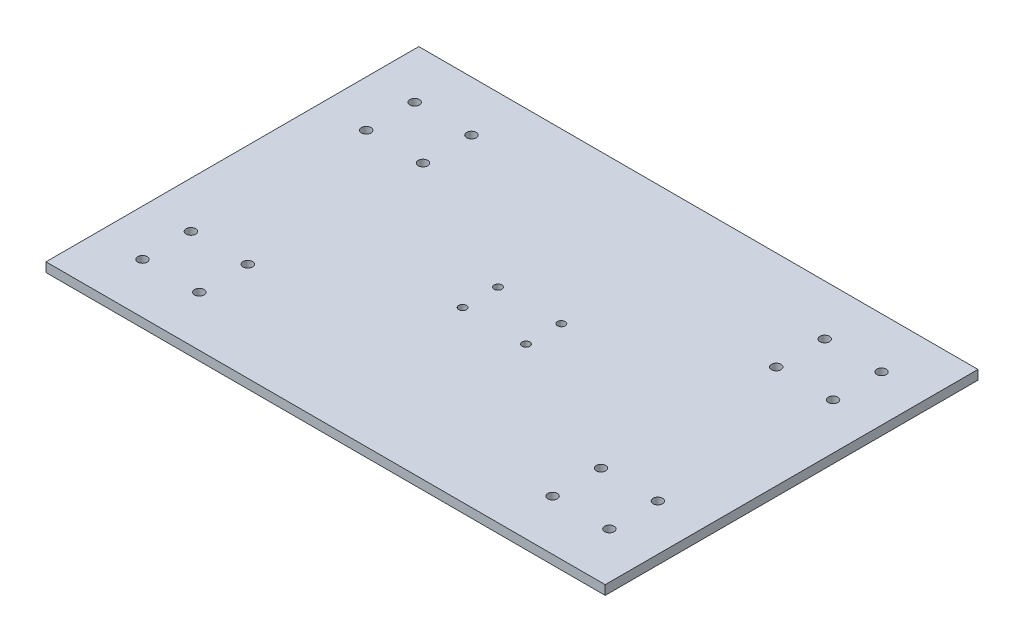
SolidWorks part; units mm, degrees
ref_plane "Front Plane" through (0, 0, 0) normal (0, 0, 1) x (1, 0, 0)
ref_plane "Top Plane" through (0, 0, 0) normal (0, 1, 0) x (1, 0, 0)
ref_plane "Right Plane" through (0, 0, 0) normal (1, 0, 0) x (0, 0, -1)
sketch "Sketch1" plane through (0, 0, 0) normal (0, 1, 0) x (1, 0, 0)
  line L1 (-150, -100) -> (150, -100)
  line L2 (-150, -100) -> (-150, 100)
  line L3 (-150, 100) -> (150, 100)
  line L4 (150, -100) -> (150, 100)
  line L5 (-150, -100) -> (150, 100) construction
  line L6 (-150, 100) -> (150, -100) construction
  point P0 (0, 0)
  dimension "D1" = 300
  dimension "D2" = 200
extrude "Boss-Extrude1" add sketch "Sketch1" along normal mid plane 5
sketch "Sketch2" plane through (0, 2.5, 0) normal (0, 1, 0) x (1, 0, 0)
  line L5 (-110, 100) -> (-110, -100)
  line L6 (-110, 100) -> (-110, -100) construction
  line L8 (110, -100) -> (110, 100)
  line L9 (110, -100) -> (110, 100) construction
  line L11 (150, 60) -> (-150, 60)
  line L12 (150, 60) -> (-150, 60) construction
  line L14 (-150, -60) -> (150, -60)
  line L15 (-150, -60) -> (150, -60) construction
  line L16 (-125.25, 73) -> (-94.75, 73) construction
  line L17 (-125.25, 73) -> (-125.25, 47) construction
  line L18 (-125.25, 47) -> (-94.75, 47) construction
  line L19 (-94.75, 73) -> (-94.75, 47) construction
  line L20 (-125.25, 73) -> (-94.75, 47) construction
  line L21 (-125.25, 47) -> (-94.75, 73) construction
  line L22 (94.75, 47) -> (125.25, 47) construction
  line L23 (94.75, 47) -> (94.75, 73) construction
  line L24 (94.75, 73) -> (125.25, 73) construction
  line L25 (125.25, 47) -> (125.25, 73) construction
  line L26 (94.75, 47) -> (125.25, 73) construction
  line L27 (94.75, 73) -> (125.25, 47) construction
  line L28 (94.75, -47) -> (125.25, -47) construction
  line L29 (94.75, -47) -> (94.75, -73) construction
  line L30 (94.75, -73) -> (125.25, -73) construction
  line L31 (125.25, -47) -> (125.25, -73) construction
  line L32 (94.75, -47) -> (125.25, -73) construction
  line L33 (94.75, -73) -> (125.25, -47) construction
  line L34 (-125.25, -73) -> (-94.75, -73) construction
  line L35 (-125.25, -73) -> (-125.25, -47) construction
  line L36 (-125.25, -47) -> (-94.75, -47) construction
  line L37 (-94.75, -73) -> (-94.75, -47) construction
  line L38 (-125.25, -73) -> (-94.75, -47) construction
  line L39 (-125.25, -47) -> (-94.75, -73) construction
  circle A0 centre (-125.25, 73) radius 2.55
  circle A1 centre (-125.25, 47) radius 2.55
  circle A2 centre (-94.75, 73) radius 2.55
  circle A3 centre (-94.75, 47) radius 2.55
  circle A4 centre (-125.25, -47) radius 2.55
  circle A5 centre (-125.25, -73) radius 2.55
  circle A6 centre (-94.75, -73) radius 2.55
  circle A7 centre (-94.75, -47) radius 2.55
  circle A8 centre (125.25, -47) radius 2.55
  circle A9 centre (94.75, -47) radius 2.55
  circle A10 centre (94.75, -73) radius 2.55
  circle A11 centre (125.25, -73) radius 2.55
  circle A12 centre (94.75, 73) radius 2.55
  circle A13 centre (94.75, 47) radius 2.55
  circle A14 centre (125.25, 73) radius 2.55
  circle A15 centre (125.25, 47) radius 2.55
  point P0 (-110, 60)
  point P13 (110, 60)
  point P18 (110, -60)
  point P23 (-110, -60)
  dimension "D13" = 5.1
  dimension "D14" = 5.1
  dimension "D15" = 5.1
  dimension "D16" = 5.1
  dimension "D17" = 5.1
  dimension "D18" = 5.1
  dimension "D19" = 5.1
  dimension "D20" = 5.1
  dimension "D21" = 5.1
  dimension "D22" = 5.1
  dimension "D23" = 5.1
  dimension "D24" = 5.1
  dimension "D25" = 5.1
  dimension "D26" = 5.1
  dimension "D27" = 5.1
  dimension "D28" = 5.1
  dimension "D1" = 40
  dimension "D5" = 30.5
  dimension "D6" = 26
  dimension "D7" = 30.5
  dimension "D8" = 26
  dimension "D9" = 26
  dimension "D10" = 30.5
  dimension "D11" = 26
  dimension "D12" = 30.5
  dimension "D2" = 40
  dimension "D3" = 40
  dimension "D4" = 40
extrude "Cut-Extrude1" cut sketch "Sketch2" against normal through all
sketch "Sketch3" plane through (0, 2.5, 0) normal (0, 1, 0) x (1, 0, 0)
  line L1 (-17, -9.5) -> (17, -9.5) construction
  line L2 (-17, -9.5) -> (-17, 9.5) construction
  line L3 (-17, 9.5) -> (17, 9.5) construction
  line L4 (17, -9.5) -> (17, 9.5) construction
  line L5 (-17, -9.5) -> (17, 9.5) construction
  line L6 (-17, 9.5) -> (17, -9.5) construction
  circle A0 centre (-17, 9.5) radius 2.05
  circle A1 centre (17, 9.5) radius 2.05
  circle A2 centre (17, -9.5) radius 2.05
  circle A3 centre (-17, -9.5) radius 2.05
  point P0 (0, 0)
  dimension "D3" = 4.1
  dimension "D4" = 4.1
  dimension "D5" = 4.1
  dimension "D6" = 4.1
  dimension "D1" = 34
  dimension "D2" = 19
extrude "Cut-Extrude2" cut sketch "Sketch3" against normal through all
